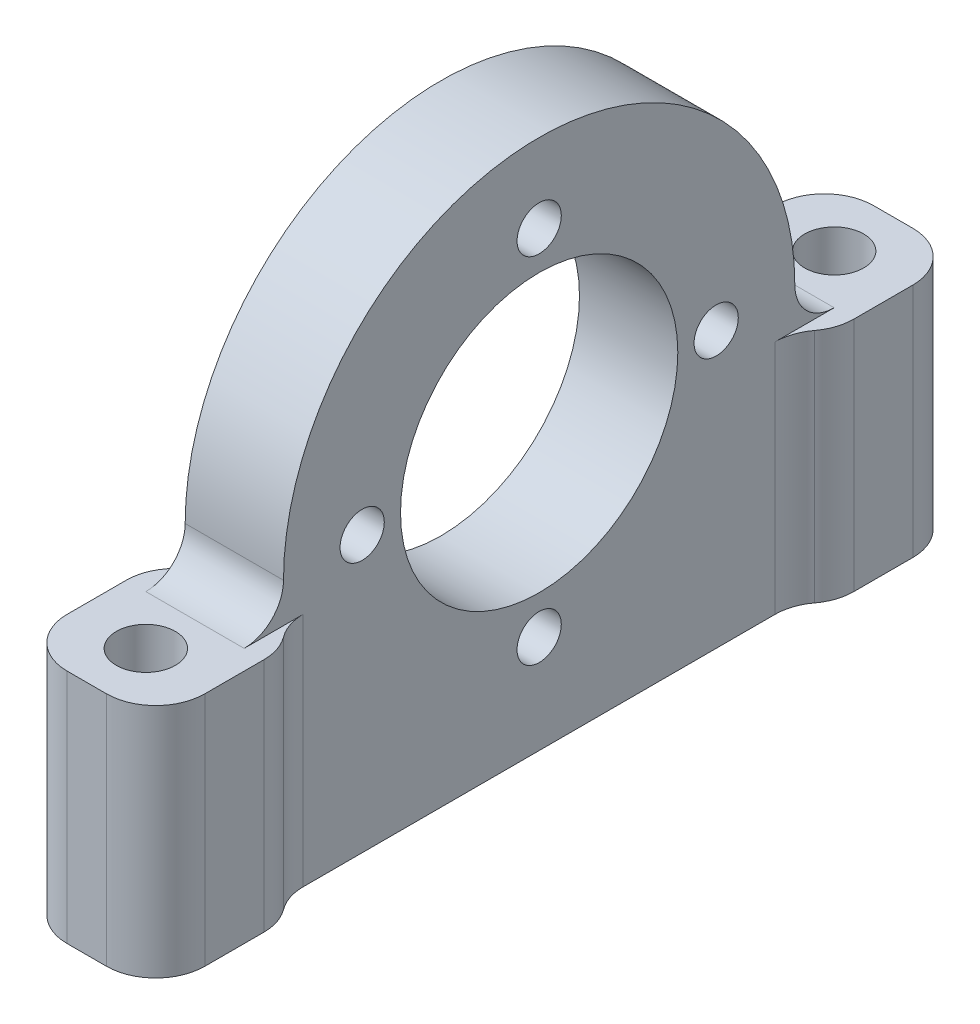
SolidWorks part; units mm, degrees
ref_plane "Front Plane" through (0, 0, 0) normal (0, 0, 1) x (1, 0, 0)
ref_plane "Top Plane" through (0, 0, 0) normal (0, 1, 0) x (1, 0, 0)
ref_plane "Right Plane" through (0, 0, 0) normal (1, 0, 0) x (0, 0, -1)
sketch "Sketch1" plane through (0, 0, 0) normal (1, 0, 0) x (0, 0, -1)
  line L0 (-13, 0) -> (-13, -3)
  line L1 (13, 0) -> (13, -3)
  line L2 (-13, -14) -> (13, -14)
  line L9 (-13, -3) -> (-13, -14)
  line L10 (13, -14) -> (13, -3)
  circle A0 centre (0, 0) radius 9 construction
  circle A1 centre (0, 9) radius 1.125
  circle A2 centre (9, 0) radius 1.125
  circle A3 centre (0, -9) radius 1.125
  circle A4 centre (-9, 0) radius 1.125
  arc A5 (-13, 0) -> (13, 0) centre (0, 0) cw
  circle A6 centre (0, 0) radius 7.05
  dimension "D1" = 18
  dimension "D2" = 2.25
  dimension "D3" = 13
  dimension "D5" = 14.1
  dimension "D4" = 14
  dimension "D7" = 26
extrude "Boss-Extrude1" add sketch "Sketch1" along normal blind 2.5 and the other way blind 2.5
sketch "Sketch2" plane through (0, 0, 0) normal (1, 0, 0) x (0, 0, -1)
  line L1 (-13, -14) -> (-20.5, -14)
  line L2 (-13, -14) -> (-13, -2)
  line L3 (-13, -2) -> (-20.5, -2)
  line L4 (-20.5, -14) -> (-20.5, -2)
  dimension "D1" = 7.5
  dimension "D2" = 12
extrude "Boss-Extrude2" add sketch "Sketch2" along normal blind 3.5 and the other way blind 3.5
fillet "Fillet3" radius 2.5 2 edges at (-3.5, -8, 20.5) (3.5, -8, 20.5)
fillet "Fillet4" radius 2.5 2 edges at (-3.5, -8, 13) (3.5, -8, 13)
fillet "Fillet5" radius 2.5 2 edges at (-2.5, -8, 13) (2.5, -8, 13)
sketch "Sketch5" plane through (0, -2, 0) normal (0, 1, 0) x (1, 0, 0)
  line L2 (-1, -20.5) -> (1, -20.5) construction
  circle A0 centre (0, -17.5) radius 1.5
  point P4 (0, 0)
  point P6 (0, 0)
  point P9 (0, -20.5)
  dimension "D1" = 3
  dimension "D2" = 3
extrude "Cut-Extrude1" cut sketch "Sketch5" against normal through all both and the other way through all
ref_plane "Plane1" through (2.5, -2, 13) normal (1, 0, 0) x (0, 0, -1)
mirror "Mirror1" about plane through (0, 0, 0) normal (0, 0, 1) of "Fillet3", "Boss-Extrude2", "Cut-Extrude1", "Fillet5", "Fillet4"
fillet "Fillet6" radius 2 2 edges at (0, -2, 13) (0, -2, -13)
